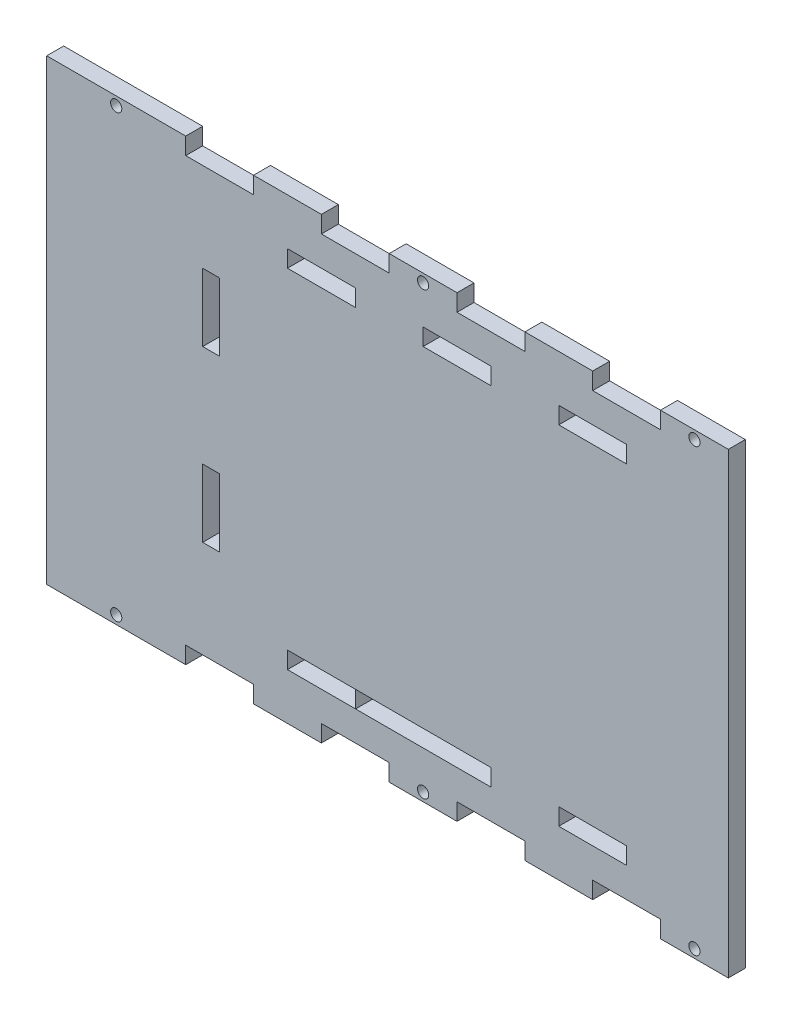
SolidWorks part; units mm, degrees
ref_plane "Front Plane" through (0, 0, 0) normal (0, 0, 1) x (1, 0, 0)
ref_plane "Top Plane" through (0, 0, 0) normal (0, 1, 0) x (1, 0, 0)
ref_plane "Right Plane" through (0, 0, 0) normal (1, 0, 0) x (0, 0, -1)
sketch "Sketch1" plane through (0, 0, 0) normal (0, 0, 1) x (1, 0, 0)
  line L1 (115.91, 155.575) -> (-139.3499, 155.575)
  line L2 (115.91, 155.575) -> (115.91, -15.875)
  line L3 (115.91, -15.875) -> (-139.3499, -15.875)
  line L4 (-139.3499, 155.575) -> (-139.3499, -15.875)
extrude "Boss-Extrude1" add sketch "Sketch1" along normal blind 6.35
sketch "Sketch2" plane through (0, 0, 6.35) normal (0, 0, 1) x (1, 0, 0)
  line L0 (-139.3499, -15.875) -> (115.91, -15.875) construction
  line L1 (-87.29, -9.525) -> (-61.89, -9.525)
  line L2 (-87.29, -9.525) -> (-87.29, -15.875)
  line L3 (-87.29, -15.875) -> (-61.89, -15.875)
  line L4 (-61.89, -9.525) -> (-61.89, -15.875)
  line L5 (-61.89, -9.525) -> (-61.89, -15.875) construction
  line L6 (115.91, 155.575) -> (-139.3499, 155.575) construction
  line L7 (-87.29, 149.225) -> (-61.89, 149.225)
  line L8 (-87.29, 149.225) -> (-87.29, 155.575)
  line L9 (-87.29, 155.575) -> (-61.89, 155.575)
  line L10 (-61.89, 149.225) -> (-61.89, 155.575)
  line L11 (-61.89, 149.225) -> (-61.89, 155.575) construction
extrude "Cut-Extrude1" cut sketch "Sketch2" against normal blind 6.35
pattern_linear "LPattern1" count 4 spacing 50.8 along (1, 0, 0) of "Cut-Extrude1"
sketch "Sketch4" plane through (0, 0, 0) normal (0, 0, -1) x (-1, 0, 0)
  line L0 (115.4535, -9.525) -> (111.1863, -15.875) construction
  line L1 (139.3499, -15.875) -> (87.29, -15.875) construction
  line L2 (111.1863, -9.525) -> (111.1863, -15.875) construction
  line L3 (111.1863, -9.525) -> (115.4535, -15.875) construction
  line L4 (115.4535, -9.525) -> (115.4535, -15.875) construction
  line L5 (-3.7436, -9.525) -> (0.5236, -15.875) construction
  line L6 (11.09, -15.875) -> (-14.31, -15.875) construction
  line L7 (0.5236, -9.525) -> (0.5236, -15.875) construction
  line L8 (0.5236, -9.525) -> (21.5469, -15.875) construction
  line L9 (-101.0764, -9.525) -> (-105.3436, -15.875) construction
  line L10 (-90.51, -15.875) -> (-115.91, -15.875) construction
  line L11 (-105.3436, -9.525) -> (-105.3436, -15.875) construction
  line L12 (-105.3436, -9.525) -> (-75.7859, -15.875) construction
  line L13 (111.1863, 149.225) -> (115.4535, 155.575) construction
  line L14 (87.29, 155.575) -> (139.3499, 155.575) construction
  line L15 (115.4535, 149.225) -> (115.4535, 155.575) construction
  line L16 (115.4535, 149.225) -> (123.8316, 155.575) construction
  line L17 (-3.7436, 149.225) -> (0.5236, 155.575) construction
  line L18 (-14.31, 155.575) -> (11.09, 155.575) construction
  line L19 (0.5236, 149.225) -> (0.5236, 155.575) construction
  line L20 (0.5236, 149.225) -> (-3.7436, 155.575) construction
  line L21 (-101.0764, 149.225) -> (-105.3436, 155.575) construction
  line L22 (-115.91, 155.575) -> (-90.51, 155.575) construction
  line L23 (-105.3436, 149.225) -> (-101.0764, 155.575) construction
  line L24 (-101.0764, 149.225) -> (-101.0764, 155.575) construction
  circle A0 centre (-103.21, -12.7) radius 2.0955
  circle A1 centre (-1.61, -12.7) radius 2.0955
  circle A2 centre (113.3199, -12.7) radius 2.0955
  circle A3 centre (113.3199, 152.4) radius 2.0955
  circle A4 centre (-1.61, 152.4) radius 2.0955
  circle A5 centre (-103.21, 152.4) radius 2.0955
  dimension "D1" = 4.191
extrude "Cut-Extrude2" cut sketch "Sketch4" against normal through all
sketch "Sketch5" plane through (0, 0, 0) normal (0, 0, -1) x (-1, 0, 0)
  line L0 (-27.01, 7.9375) -> (-1.61, 7.9375) construction
  line L1 (-77.81, 1.5875) -> (-52.41, 1.5875)
  line L2 (-77.81, 1.5875) -> (-77.81, 7.9375)
  line L3 (-77.81, 7.9375) -> (-52.41, 7.9375)
  line L4 (-52.41, 1.5875) -> (-52.41, 7.9375)
  line L5 (-27.01, 1.5875) -> (23.6805, 1.5875)
  line L6 (-27.01, 1.5875) -> (-27.01, 7.9375)
  line L7 (-27.01, 7.9375) -> (23.6805, 7.9375)
  line L8 (23.6805, 1.5875) -> (23.6805, 7.9375)
  line L9 (80.94, 90.4875) -> (80.94, 115.8875) construction
  line L10 (23.79, 1.5875) -> (49.19, 1.5875)
  line L11 (23.79, 1.5875) -> (23.79, 7.9375)
  line L12 (23.79, 7.9375) -> (49.19, 7.9375)
  line L13 (49.19, 1.5875) -> (49.19, 7.9375)
  line L14 (74.59, 26.9875) -> (80.94, 26.9875)
  line L15 (74.59, 26.9875) -> (74.59, 52.3875)
  line L16 (74.59, 52.3875) -> (80.94, 52.3875)
  line L17 (80.94, 26.9875) -> (80.94, 52.3875)
  line L18 (74.59, 90.4875) -> (80.94, 90.4875)
  line L19 (74.59, 90.4875) -> (74.59, 115.8875)
  line L20 (74.59, 115.8875) -> (80.94, 115.8875)
  line L21 (80.94, 90.4875) -> (80.94, 115.8875)
  line L22 (80.94, 115.8875) -> (74.59, 115.8875) construction
  line L24 (23.79, 131.7625) -> (49.19, 131.7625)
  line L25 (23.79, 131.7625) -> (23.79, 138.1125)
  line L26 (23.79, 138.1125) -> (49.19, 138.1125)
  line L27 (49.19, 131.7625) -> (49.19, 138.1125)
  line L28 (-27.01, 131.7625) -> (-1.61, 131.7625)
  line L29 (-27.01, 131.7625) -> (-27.01, 138.1125)
  line L30 (-27.01, 138.1125) -> (-1.61, 138.1125)
  line L31 (-1.61, 131.7625) -> (-1.61, 138.1125)
  line L32 (-52.41, 138.1125) -> (-77.81, 138.1125)
  line L33 (-52.41, 138.1125) -> (-52.41, 131.7625)
  line L34 (-52.41, 131.7625) -> (-77.81, 131.7625)
  line L35 (-77.81, 138.1125) -> (-77.81, 131.7625)
extrude "Cut-Extrude3" cut sketch "Sketch5" against normal blind 6.35
